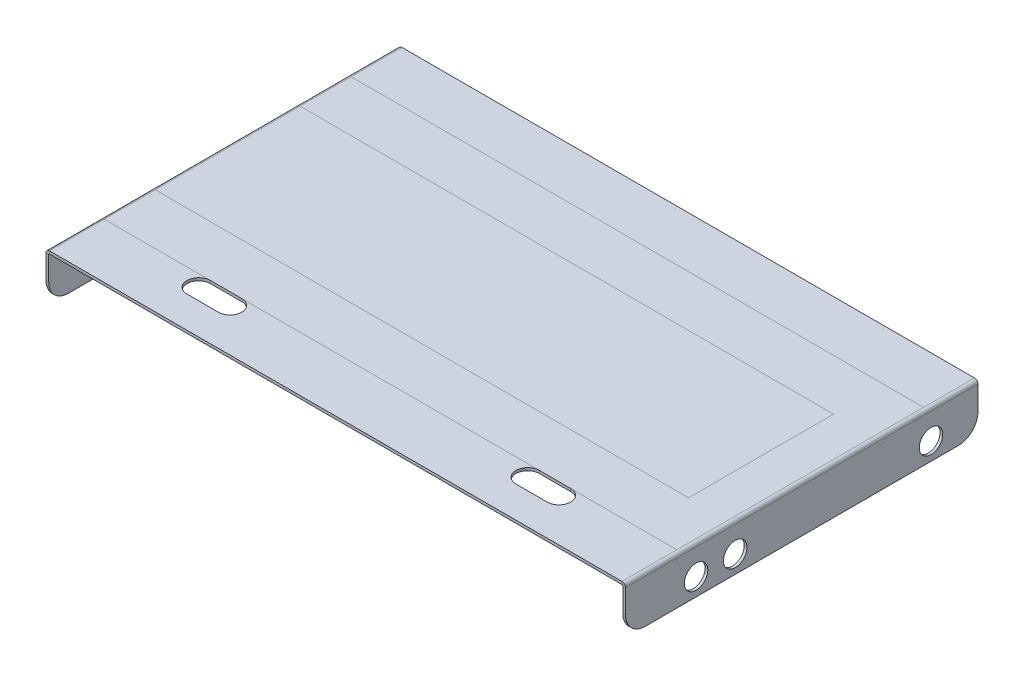
SolidWorks part; units mm, degrees
note: The reader was unsure of these and kept them because the rebuilt part matched: flange length of "边线-法兰1".
ref_plane "前视基准面" through (0, 0, 0) normal (0, 0, 1) x (1, 0, 0)
ref_plane "上视基准面" through (0, 0, 0) normal (0, 1, 0) x (1, 0, 0)
ref_plane "右视基准面" through (0, 0, 0) normal (1, 0, 0) x (0, 0, -1)
sketch "草图1" plane through (0, 0, 0) normal (0, 1, 0) x (1, 0, 0)
  line L0 (-46, -34) -> (-38, -34) construction
  line L1 (-74, 45) -> (74, 45)
  line L2 (-74, 45) -> (-74, -45)
  line L3 (-74, -45) -> (74, -45)
  line L4 (74, 45) -> (74, -45)
  line L5 (-74, 45) -> (74, -45) construction
  line L6 (-74, -45) -> (74, 45) construction
  line L7 (-46, -31) -> (-38, -31)
  line L8 (-46, -37) -> (-38, -37)
  line L9 (38, -34) -> (46, -34) construction
  line L10 (38, -31) -> (46, -31)
  line L11 (38, -37) -> (46, -37)
  arc A0 (-46, -31) -> (-46, -37) centre (-46, -34) ccw
  arc A1 (-38, -37) -> (-38, -31) centre (-38, -34) ccw
  arc A2 (38, -31) -> (38, -37) centre (38, -34) ccw
  arc A3 (46, -37) -> (46, -31) centre (46, -34) ccw
  point P0 (0, 0)
  point P8 (-42, -34)
  point P13 (42, -34)
  point P20 (-42, -37)
  dimension "D7" = 28
  dimension "D8" = 28
  dimension "D1" = 148
  dimension "D2" = 90
  dimension "D3" = 8
  dimension "D4" = 8
  dimension "D5" = 6
  dimension "D6" = 6
  dimension "D9" = 8
base flange "基体-法兰1" sketch "草图1" thickness 0.7 reverse thickness direction no parameters "D1"=0.2
edge flange "边线-法兰1" sketch "草图12" flange profiles "草图12", "草图13" flange angle 90 flange length 12 flange position material inside bend radius 0.2 thickness 0.7 relief rectangular parameters "D6"=10, "D8"=1
sketch "草图12" plane through (74, -0.7, 0) normal (1, 0, 0) x (0, 0, 1)
  line L2 (-45, 0) -> (-45, 11.3)
  line L3 (-45, 11.3) -> (45, 11.3)
  line L4 (45, 11.3) -> (45, 0)
  line L7 (45, 0) -> (-45, 0) construction
  line L8 (45, 0) -> (-45, 0)
  line L9 (45, -0.7) -> (-45, -0.7) construction
  circle A0 centre (-33, 6.8) radius 3
  circle A1 centre (17, 6.8) radius 3
  circle A2 centre (27, 6.8) radius 3
  dimension "D1" = 6
  dimension "D2" = 4.5
  dimension "D3" = 12
  dimension "D4" = 50
  dimension "D5" = 7.5
  dimension "D6" = 10
sketch "草图13" plane through (-74, -0.7, 0) normal (-1, 0, 0) x (0, 0, -1)
  line L2 (-45, 0) -> (-45, 11.3)
  line L3 (-45, 11.3) -> (45, 11.3)
  line L4 (45, 11.3) -> (45, 0)
  line L7 (45, 0) -> (-45, 0) construction
  line L8 (45, 0) -> (-45, 0)
bend "边线折弯1" bend radius 0.2 bend angle 90 parameters "D5"=1
bend "边线折弯2" bend radius 0.2 bend angle 90 parameters "D5"=2
fillet "圆角2" radius 5 4 edges at (73.65, -12, -45) (73.65, -12, 45) (-73.65, -12, 45) (-73.65, -12, -45)
sketch "草图15" plane through (-74, 0, 0) normal (-1, 0, 0) x (0, 0, 1)
  circle A0 centre (-33, -7.5) radius 3
  circle A1 centre (17, -7.5) radius 3
  circle A2 centre (27, -7.5) radius 3
  dimension "D1" = 6
  dimension "D2" = 10
  dimension "D3" = 50
extrude "切除-拉伸1" cut sketch "草图15" against normal blind 10
sketch "草图17" plane through (0, 0, 0) normal (0, 1, 0) x (1, 0, 0)
  line L0 (-73.1, 32) -> (73.1, 32)
  line L4 (-73.1, -31) -> (73.1, -31)
  line L6 (-46, -31) -> (-38, -31) construction
  line L7 (-73.1, -31) -> (-73.1, -18)
  line L8 (-73.1, 45) -> (-73.1, -45) construction
  line L9 (73.1, -31) -> (73.1, 32)
  line L10 (73.1, -45) -> (73.1, 45) construction
  line L11 (-73.1, 19) -> (63.1, 19)
  line L12 (63.1, 19) -> (63.1, -18)
  line L13 (63.1, -18) -> (-73.1, -18)
  line L14 (-73.1, 19) -> (-73.1, 32)
  dimension "D1" = 0
  dimension "D2" = 63
  dimension "D3" = 13
  dimension "D4" = 13
  dimension "D5" = 10
split "分割1" trim tools "草图17" bodies to split 109 resulting bodies 113 114
sketch "折弯-线1" [suppressed] plane through (0, 0, 0) normal (0, 1, 0) x (1, 0, 0)
sketch "边界框1" [suppressed] plane through (0, 0, 0) normal (0, 1, 0) x (1, 0, 0)
sheet metal parameters "钣金6" thickness 0.7 parameters "D1"=0.2
flat pattern "平板型式6" [suppressed]
sketch "折弯-线2" plane through (0, 0, 0) normal (0, 1, 0) x (1, 0, 0)
sketch "边界框2" [suppressed] plane through (0, 0, 0) normal (0, 1, 0) x (1, 0, 0)
sheet metal parameters "钣金7" thickness 0.7 parameters "D1"=0.2
flat pattern "平板型式6" [suppressed]
sketch "折弯-线2" plane through (0, 0, 0) normal (0, 1, 0) x (1, 0, 0)
sketch "边界框2" [suppressed] plane through (0, 0, 0) normal (0, 1, 0) x (1, 0, 0)
bend of the flat pattern "展平-<边线折弯1>1"
bend of the flat pattern "展平-<边线折弯2>1"
sheet metal parameters "钣金9" thickness 0.7 parameters "D1"=0.2
flat pattern "平板型式6" [suppressed]
sketch "折弯-线2" plane through (0, 0, 0) normal (0, 1, 0) x (1, 0, 0)
sketch "边界框2" [suppressed] plane through (0, 0, 0) normal (0, 1, 0) x (1, 0, 0)
bend of the flat pattern "展平-<边线折弯1>1"
bend of the flat pattern "展平-<边线折弯2>1"
sheet metal parameters "钣金13" thickness 0.7 parameters "D1"=0.2
flat pattern "平板型式13"
sketch "折弯-线3" plane through (0, 0, 0) normal (0, 1, 0) x (1, 0, 0)
  line L0 (-74, 45) -> (-74, -45) construction
  line L1 (74, -45) -> (74, 45) construction
  line L2 (-74, 45) -> (-74, -45) construction
  line L3 (74, -45) -> (74, 45) construction
sketch3d "边界框3" [suppressed]
  line L0 (-86, -45, 0) -> (86, -45, 0) construction
  line L1 (-86, 45, 0) -> (86, 45, 0) construction
  line L2 (-86, -45, 0) -> (-86, 45, 0) construction
  line L3 (86, -45, 0) -> (86, 45, 0) construction
bend of the flat pattern "展平-<边线折弯1>2"
bend of the flat pattern "展平-<边线折弯2>2"
sheet metal parameters "钣金14" thickness 0.7 parameters "D1"=0.2
flat pattern "平板型式14"
sketch "折弯-线4" plane through (0, 0, 0) normal (0, 1, 0) x (1, 0, 0)
sketch3d "边界框4" [suppressed]
  line L0 (73.1, -31, 0) -> (-73.1, -31, 0) construction
  line L1 (73.1, 32, 0) -> (-73.1, 32, 0) construction
  line L2 (73.1, -31, 0) -> (73.1, 32, 0) construction
  line L3 (-73.1, -31, 0) -> (-73.1, 32, 0) construction
